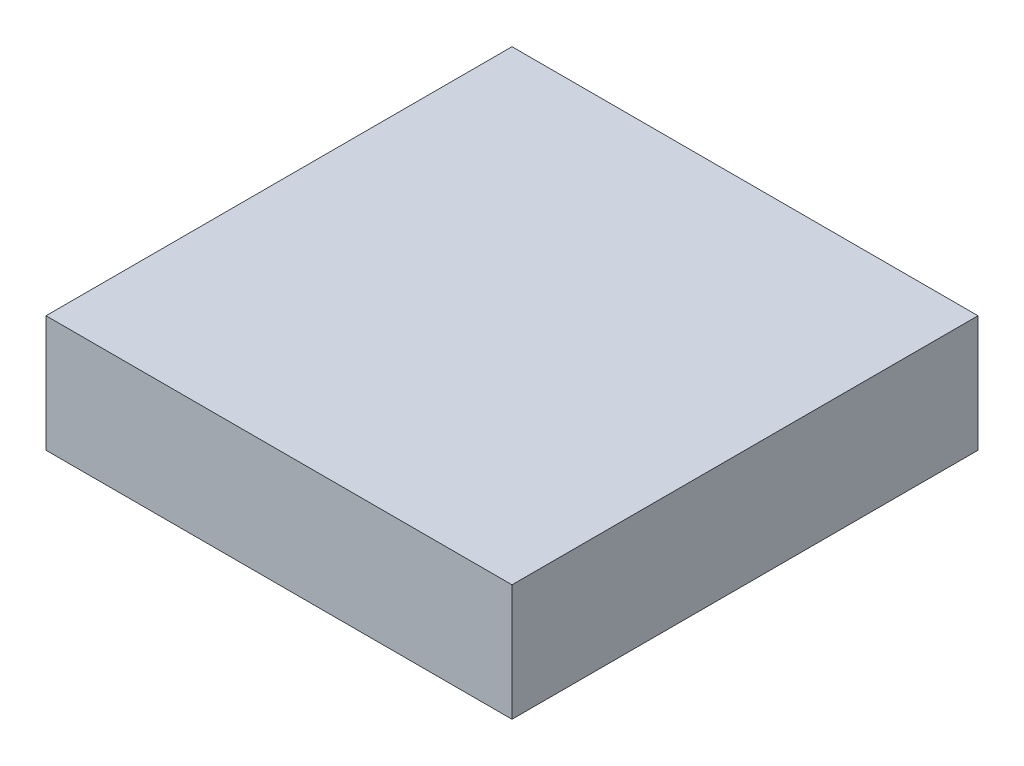
SolidWorks part; units mm, degrees
material "Polyurethane Foam Rigid"
ref_plane "Front Plane" through (0, 0, 0) normal (0, 0, 1) x (1, 0, 0)
ref_plane "Top Plane" through (0, 0, 0) normal (0, 1, 0) x (1, 0, 0)
ref_plane "Right Plane" through (0, 0, 0) normal (1, 0, 0) x (0, 0, -1)
sketch "Sketch1" plane through (0, 0, 0) normal (0, 1, 0) x (1, 0, 0)
  line L1 (-50.8, -50.8) -> (50.8, -50.8)
  line L2 (-50.8, -50.8) -> (-50.8, 50.8)
  line L3 (-50.8, 50.8) -> (50.8, 50.8)
  line L4 (50.8, -50.8) -> (50.8, 50.8)
  line L5 (-50.8, -50.8) -> (50.8, 50.8) construction
  line L6 (-50.8, 50.8) -> (50.8, -50.8) construction
  point P0 (0, 0)
  dimension "D1" = 101.6
  dimension "D2" = 101.6
extrude "Boss-Extrude1" add sketch "Sketch1" along normal blind 25.4
